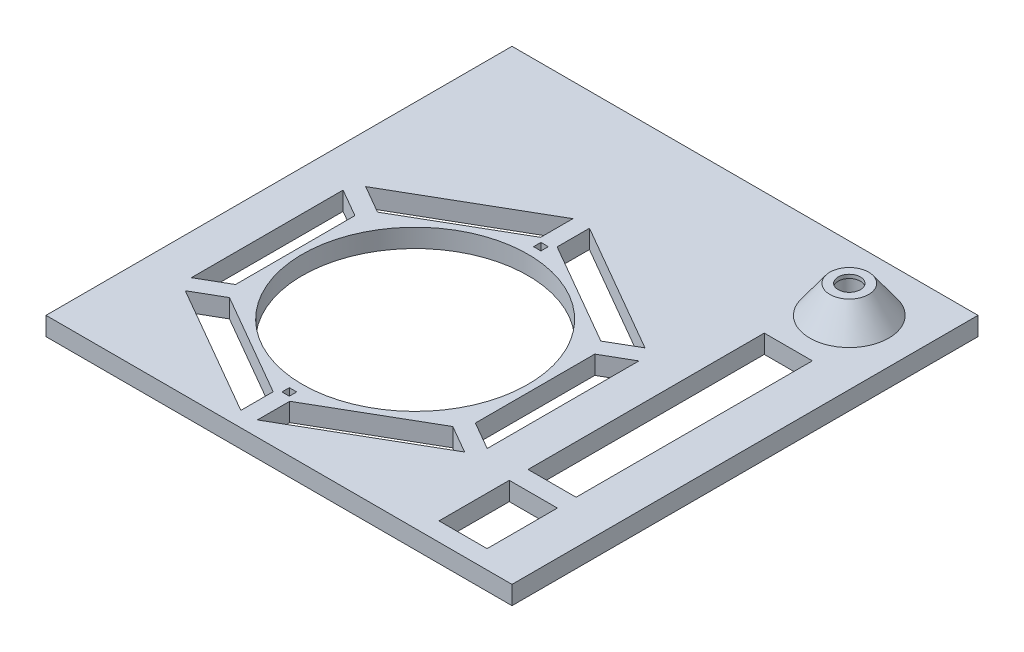
SolidWorks part; units mm, degrees
ref_plane "Front Plane" through (0, 0, 0) normal (0, 0, 1) x (1, 0, 0)
ref_plane "Top Plane" through (0, 0, 0) normal (0, 1, 0) x (1, 0, 0)
ref_plane "Right Plane" through (0, 0, 0) normal (1, 0, 0) x (0, 0, -1)
sketch "Sketch1" plane through (0, 0, 0) normal (0, 1, 0) x (1, 0, 0)
  line L1 (0, 0) -> (126, 0)
  line L2 (0, 0) -> (0, 126)
  line L3 (0, 126) -> (126, 126)
  line L4 (126, 0) -> (126, 126)
  dimension "D1" = 126
  dimension "D2" = 126
extrude "Boss-Extrude1" add sketch "Sketch1" along normal blind 5
sketch "Sketch3" plane through (0, 5, 0) normal (0, 1, 0) x (1, 0, 0)
  line L0 (108.6, 121.1) -> (108.6, 96.1) construction
  circle A0 centre (108.6, 108.6) radius 12.5
extrude "Boss-Extrude2" add sketch "Sketch3" along normal blind 7.5
sketch "Sketch4" plane through (0, 0, 0) normal (0, -1, 0) x (1, 0, 0)
  circle A1 centre (108.6, -108.6) radius 3.45
  dimension "D1" = 6.9
extrude "Cut-Extrude1" cut sketch "Sketch4" against normal blind 11.5
sketch "Sketch6" plane through (0, 12.5, 0) normal (0, 1, 0) x (1, 0, 0)
  line L0 (108.6, 121.1) -> (108.6, 96.1) construction
  circle A0 centre (108.6, 108.6) radius 12.5 construction
  circle A1 centre (108.6, 108.6) radius 3
  dimension "D1" = 6
extrude "Cut-Extrude2" cut sketch "Sketch6" against normal through all
chamfer "Chamfer1" distance 10 angle 36 1 edges at (108.6, 12.5, -96.1) first distance on face at (108.6, 12.5, -96.1)
sketch "Sketch8" plane through (0, 5, 0) normal (0, 1, 0) x (1, 0, 0)
  line L7 (114.2633, 24) -> (101.2633, 24)
  line L8 (114.2633, 24) -> (114.2633, 5)
  line L9 (114.2633, 5) -> (101.2633, 5)
  line L10 (101.2633, 24) -> (101.2633, 5)
  line L11 (114.2633, 24) -> (101.2633, 5) construction
  line L12 (114.2633, 5) -> (101.2633, 24) construction
  line L13 (114.2633, 24) -> (101.2633, 24)
  line L21 (114.2633, 29.0695) -> (101.2633, 29.0695)
  line L22 (114.2633, 29.0695) -> (114.2633, 92.9492)
  line L23 (114.2633, 92.9492) -> (101.2633, 92.9492)
  line L24 (101.2633, 29.0695) -> (101.2633, 92.9492)
  line L25 (114.2633, 29.0695) -> (101.2633, 92.9492) construction
  line L26 (114.2633, 92.9492) -> (101.2633, 29.0695) construction
  point P11 (107.7633, 14.5)
  point P17 (107.7633, 61.0093)
  dimension "D2" = 13
  dimension "D3" = 19
extrude "Cut-Extrude3" cut sketch "Sketch8" against normal through all contours L24 L21 L22 L23 | L7 L10 L9 L8 region at (107.7633, 5, -14.5) region at (107.7633, 5, -61.0093)
sketch "Sketch9" plane through (0, 5, 0) normal (0, 1, 0) x (1, 0, 0)
  circle A0 centre (50.8372, 48.9746) radius 30.5
  dimension "D1" = 61
extrude "Cut-Extrude4" cut sketch "Sketch9" against normal through all
sketch "Sketch10" plane through (0, 5, 0) normal (0, 1, 0) x (1, 0, 0)
  line L0 (50.8372, 79.4746) -> (50.8372, 18.4746) construction
  line L2 (18.3372, 67.7385) -> (18.3372, 30.2107)
  line L3 (18.3372, 30.2107) -> (50.8372, 11.4468)
  line L4 (50.8372, 11.4468) -> (83.3372, 30.2107)
  line L5 (83.3372, 30.2107) -> (83.3372, 67.7385)
  line L6 (83.3372, 67.7385) -> (50.8372, 86.5024)
  line L7 (50.8372, 86.5024) -> (18.3372, 67.7385)
  circle A0 centre (50.8372, 48.9746) radius 30.5 construction
  circle A1 centre (50.8372, 48.9746) radius 32.5 construction
  dimension "D1" = 65
sketch "Sketch11" plane through (0, 5, 0) normal (0, 1, 0) x (1, 0, 0)
  line L0 (50.8372, 79.4746) -> (50.8372, 86.5024) construction
  line L1 (50.8372, 11.4468) -> (50.8372, 18.4746) construction
  line L2 (51.8372, 83.9885) -> (49.8372, 83.9885)
  line L3 (51.8372, 83.9885) -> (51.8372, 81.9885)
  line L4 (51.8372, 81.9885) -> (49.8372, 81.9885)
  line L5 (49.8372, 83.9885) -> (49.8372, 81.9885)
  line L6 (51.8372, 83.9885) -> (49.8372, 81.9885) construction
  line L7 (51.8372, 81.9885) -> (49.8372, 83.9885) construction
  line L9 (51.8372, 13.9607) -> (49.8372, 13.9607)
  line L10 (51.8372, 13.9607) -> (51.8372, 15.9607)
  line L11 (51.8372, 15.9607) -> (49.8372, 15.9607)
  line L12 (49.8372, 13.9607) -> (49.8372, 15.9607)
  line L13 (51.8372, 13.9607) -> (49.8372, 15.9607) construction
  line L14 (51.8372, 15.9607) -> (49.8372, 13.9607) construction
  point P4 (50.8372, 82.9885)
  point P13 (50.8372, 14.9607)
  dimension "D1" = 2
  dimension "D2" = 2
  dimension "D3" = 2
  dimension "D4" = 2
extrude "Cut-Extrude5" cut sketch "Sketch11" against normal blind 3
sketch "Sketch13" plane through (0, 5, 0) normal (0, 1, 0) x (1, 0, 0)
  line L1 (126, 126) -> (0, 126) construction
  line L2 (50.8372, 126) -> (50.8372, 0) construction
  line L3 (0, 0) -> (126, 0) construction
  line L4 (0, 126) -> (0, 0) construction
  line L5 (0, 86.5024) -> (126, 86.5024) construction
  line L6 (126, 0) -> (126, 126) construction
  line L7 (18.3372, 126) -> (18.3372, 0) construction
  line L9 (83.3372, 126) -> (83.3372, 0) construction
sketch "Sketch14" plane through (0, 5, 0) normal (0, 1, 0) x (1, 0, 0)
  line L0 (53.0728, 93.8719) -> (88.6016, 73.3593)
  line L12 (48.6016, 85.1295) -> (20.6439, 68.9881)
  line L13 (20.6439, 68.9881) -> (13.0728, 73.3593)
  line L17 (88.6016, 73.3593) -> (81.0304, 68.9881)
  line L18 (81.0304, 68.9881) -> (53.0728, 85.1295)
  line L23 (53.0728, 85.1295) -> (53.0728, 93.8719)
  line L24 (90.8372, 69.4871) -> (90.8372, 28.462)
  line L29 (90.8372, 28.462) -> (83.266, 32.8332)
  line L30 (83.266, 32.8332) -> (83.266, 65.116)
  line L35 (83.266, 65.116) -> (90.8372, 69.4871)
  line L36 (88.6016, 24.5899) -> (53.0728, 4.0773)
  line L42 (48.6016, 93.8719) -> (48.6016, 85.1295)
  line L43 (13.0728, 73.3593) -> (48.6016, 93.8719)
  line L44 (53.0728, 4.0773) -> (53.0728, 12.8197)
  line L45 (53.0728, 12.8197) -> (81.0304, 28.961)
  line L46 (81.0304, 28.961) -> (88.6016, 24.5899)
  line L47 (48.6016, 4.0773) -> (13.0728, 24.5899)
  line L48 (13.0728, 24.5899) -> (20.6439, 28.961)
  line L49 (20.6439, 28.961) -> (48.6016, 12.8197)
  line L50 (48.6016, 12.8197) -> (48.6016, 4.0773)
  line L51 (10.8372, 28.462) -> (10.8372, 69.4871)
  line L52 (10.8372, 69.4871) -> (18.4083, 65.116)
  line L53 (18.4083, 65.116) -> (18.4083, 32.8332)
  line L54 (18.4083, 32.8332) -> (10.8372, 28.462)
  dimension "D1" = 6
extrude "Cut-Extrude6" cut sketch "Sketch14" against normal through all
